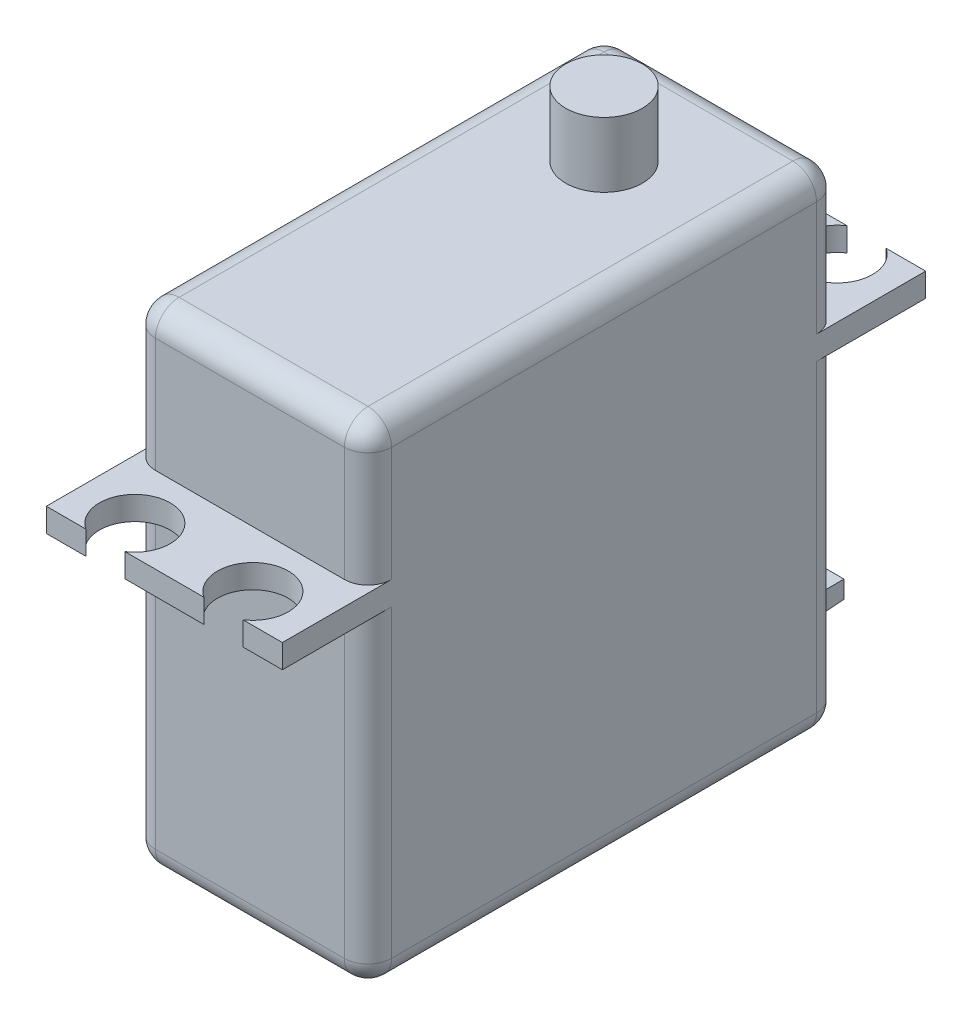
SolidWorks part; units mm, degrees
material "AISI 304"
ref_plane "Front" through (0, 0, 0) normal (0, 0, 1) x (1, 0, 0)
ref_plane "Top" through (0, 0, 0) normal (0, 1, 0) x (1, 0, 0)
ref_plane "Right" through (0, 0, 0) normal (1, 0, 0) x (0, 0, -1)
sketch "Sketch1" plane through (0, 0, 0) normal (0, 1, 0) x (1, 0, 0)
  line L1 (-10, -20) -> (10, -20)
  line L2 (-10, -20) -> (-10, 20)
  line L3 (-10, 20) -> (10, 20)
  line L4 (10, -20) -> (10, 20)
  line L5 (-10, -20) -> (10, 20) construction
  line L6 (-10, 20) -> (10, -20) construction
  point P0 (0, 0)
  dimension "D1" = 20
  dimension "D2" = 40
extrude "Boss-Extrude1" add sketch "Sketch1" against normal blind 27.8 and the other way blind 13.7
sketch "Sketch4" plane through (0, 0, 0) normal (0, 1, 0) x (1, 0, 0)
  line L0 (10, -20) -> (10, 20) construction
  line L1 (-10, -27.25) -> (10, -27.25)
  line L2 (-10, -27.25) -> (-10, 27.25)
  line L3 (-10, 27.25) -> (10, 27.25)
  line L4 (10, -27.25) -> (10, 27.25)
  line L5 (-10, -27.25) -> (10, 27.25) construction
  line L6 (-10, 27.25) -> (10, -27.25) construction
  point P0 (0, 0)
  dimension "D1" = 54.5
extrude "Boss-Extrude2" add sketch "Sketch4" along normal blind 2
sketch "Sketch5" plane through (0, 2, 0) normal (0, 1, 0) x (1, 0, 0)
  line L0 (-5, 24.75) -> (5, 24.75) construction
  line L1 (5, 24.75) -> (5, -24.75) construction
  line L2 (5, -24.75) -> (-5, -24.75) construction
  line L3 (-5, -24.75) -> (-5, 24.75) construction
  circle A0 centre (-5, 24.75) radius 3
  circle A1 centre (5, 24.75) radius 3
  circle A2 centre (-5, -24.75) radius 3
  circle A3 centre (5, -24.75) radius 3
  point P8 (-5, 0)
  point P9 (0, 24.75)
  dimension "D3" = 6
  dimension "D1" = 10
  dimension "D2" = 49.5
extrude "Cut-Extrude1" cut sketch "Sketch5" against normal through all
sketch "Sketch6" plane through (0, 13.7, 0) normal (0, 1, 0) x (1, 0, 0)
  line L0 (0, 10) -> (0, 27.25) construction
  line L1 (3.3417, 27.25) -> (-3.3417, 27.25) construction
  circle A0 centre (0, 10) radius 3.25
  dimension "D2" = 6.5
  dimension "D1" = 17.25
extrude "Boss-Extrude3" add sketch "Sketch6" along normal blind 5.5
sketch "Sketch7" plane through (0, 0, -20) normal (0, 0, -1) x (-1, 0, 0)
  line L1 (-3.3333, -25.8) -> (3.3333, -25.8)
  line L2 (-3.3333, -25.8) -> (-3.3333, -23.8)
  line L3 (-3.3333, -23.8) -> (3.3333, -23.8)
  line L4 (3.3333, -25.8) -> (3.3333, -23.8)
  line L5 (-10, -27.8) -> (10, -27.8) construction
  point P4 (0, -25.8)
  point P7 (0, -27.8)
  dimension "D1" = 2
  dimension "D2" = 6.6667
  dimension "D3" = 2
extrude "Boss-Extrude4" add sketch "Sketch7" along normal up to surface (7.25 mm away) draft 2
fillet "Fillet1" radius 2 16 edges at (0, 13.7, -20) (0, 13.7, 20) (-10, 13.7, 0) (10, 13.7, 0) (10, 7.85, 20) (0, -27.8, 20) (10, -27.8, 0) (10, -13.9, 20) (0, -27.8, -20) (-10, -27.8, 0) (-10, -13.9, 20) (-10, 7.85, 20) (-10, 7.85, -20) (-10, -13.9, -20) (10, 7.85, -20) (10, -13.9, -20)
